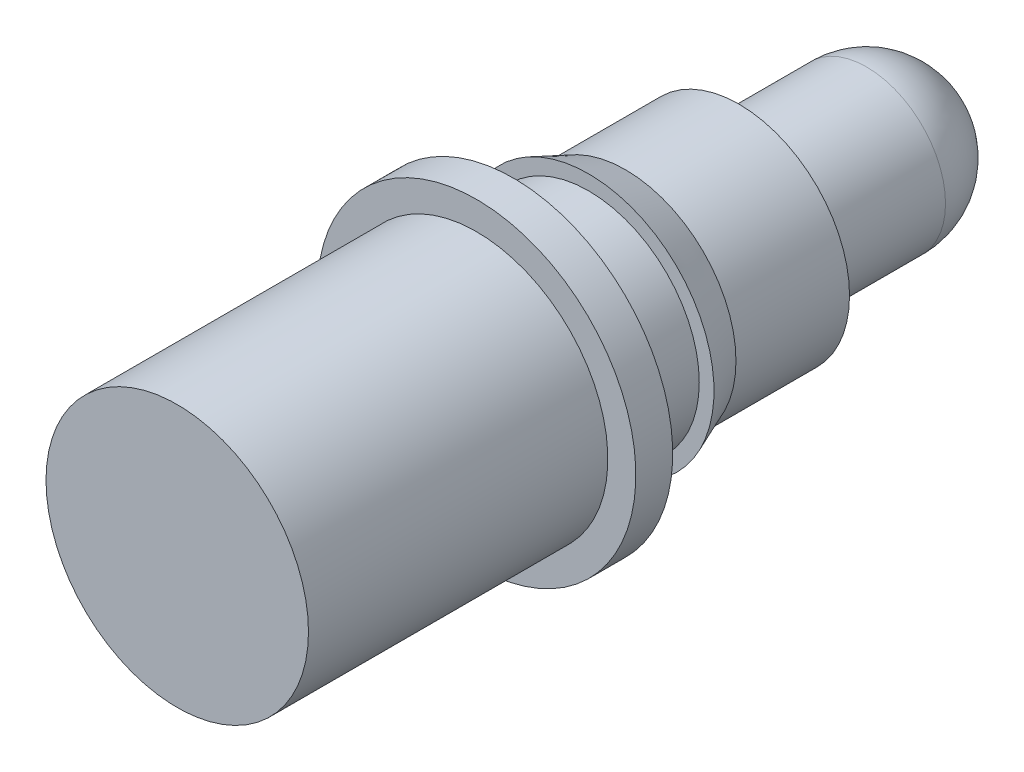
SolidWorks part; units mm, degrees
ref_plane "Front Plane" through (0, 0, 0) normal (0, 0, 1) x (1, 0, 0)
ref_plane "Top Plane" through (0, 0, 0) normal (0, 1, 0) x (1, 0, 0)
ref_plane "Right Plane" through (0, 0, 0) normal (1, 0, 0) x (0, 0, -1)
sketch "Sketch1" plane through (0, 0, 0) normal (0, 0, 1) x (1, 0, 0)
  circle A0 centre (0, 0) radius 0.89
extrude "base" add sketch "Sketch1" along normal blind 2.03
sketch "Sketch2" plane through (0, 0, 0) normal (0, 0, -1) x (-1, 0, 0)
  circle A0 centre (0, 0) radius 1.08
extrude "flange" add sketch "Sketch2" along normal blind 0.25
sketch "Sketch4" plane through (0, 0, -0.25) normal (0, 0, -1) x (-1, 0, 0)
  circle A0 centre (0, 0) radius 0.75
extrude "Boss-Extrude1" add sketch "Sketch4" along normal blind 0.51 separate body
sketch "Sketch7" plane through (0, 0, -0.76) normal (0, 0, -1) x (-1, 0, 0)
  circle A0 centre (0, 0) radius 0.85
extrude "Boss-Extrude4" add sketch "Sketch7" along normal blind 0.25 draft 22
sketch "Sketch8" plane through (0, 0, -1.01) normal (0, 0, -1) x (-1, 0, 0)
  circle A0 centre (0, 0) radius 0.749
extrude "Boss-Extrude5" add sketch "Sketch8" along normal blind 0.77
sketch "Sketch3" plane through (0, 0, -0.25) normal (0, 0, -1) x (-1, 0, 0)
  circle A0 centre (0, 0) radius 0.535
extrude "pin" add sketch "Sketch3" along normal blind 2.395 separate body
dome "Dome1" faces to dome 1 distance 0.535 reverse direction no elliptical dome no face at (-0.535, 0, -2.645) parameters "D1"=0.535
